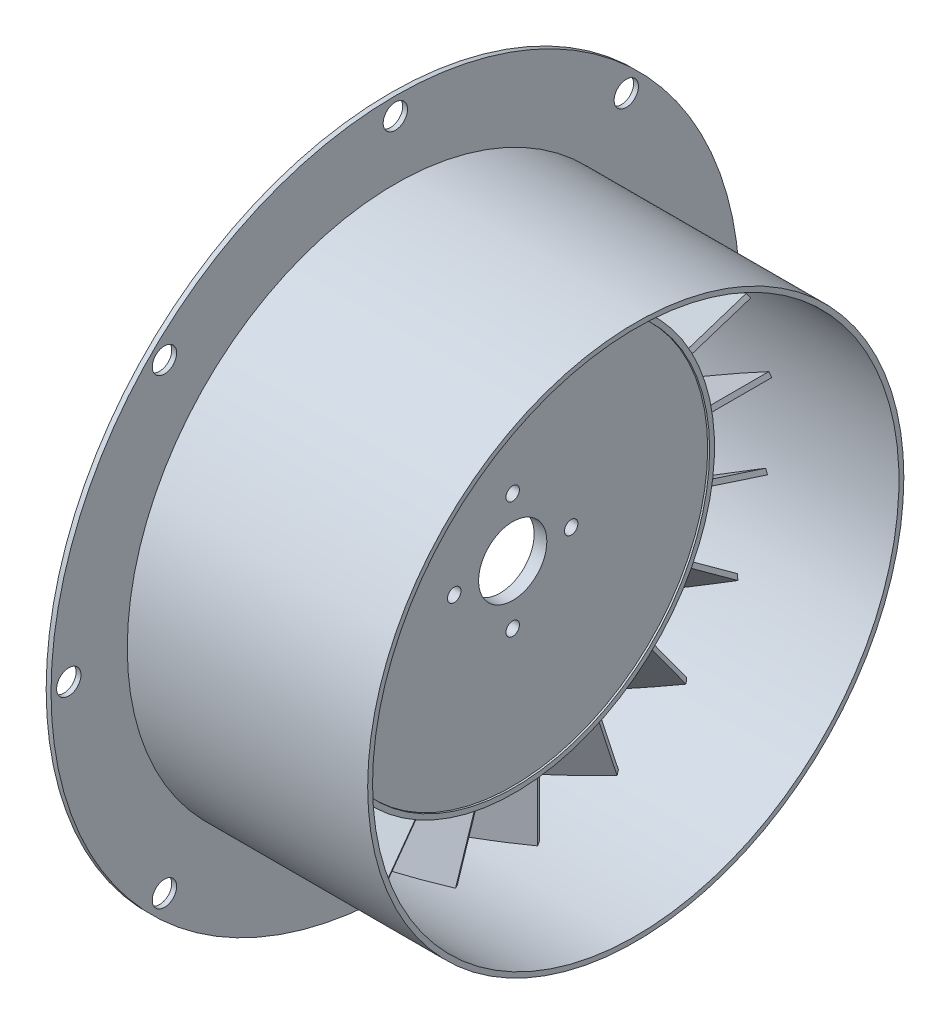
SolidWorks part; units mm, degrees
ref_plane "Front Plane" through (0, 0, 0) normal (0, 0, 1) x (1, 0, 0)
ref_plane "Top Plane" through (0, 0, 0) normal (0, 1, 0) x (1, 0, 0)
ref_plane "Right Plane" through (0, 0, 0) normal (1, 0, 0) x (0, 0, -1)
sketch "Sketch1" plane through (0, 0, 0) normal (0, 1, 0) x (1, 0, 0)
  line L0 (3.302, 0) -> (3.302, 50.8)
  line L1 (3.302, 50.8) -> (3.81, 50.8)
  line L2 (3.81, 50.8) -> (3.81, 52.07)
  line L3 (3.81, 52.07) -> (-25.4, 52.07)
  line L4 (-25.4, 52.07) -> (-25.4, 50.8)
  line L5 (-25.4, 50.8) -> (0, 50.8)
  line L6 (0, 50.8) -> (0, 0)
  line L7 (0, 0) -> (3.302, 0)
  dimension "D1" = 3.302
  dimension "D2" = 1.27
  dimension "D3" = 50.8
  dimension "D4" = 29.21
  dimension "D5" = 25.4
revolve "Revolve1" add sketch "Sketch1" angle 360 about L7
ref_plane "Plane1" through (0, 0, 83.82) normal (0, 0, 1) x (1, 0, 0)
sketch "Sketch2" plane through (0, 0, 83.82) normal (0, 0, 1) x (1, 0, 0)
  line L0 (-24.3107, 7.0701) -> (2.0857, -8.1699)
  line L1 (2.0857, -8.1699) -> (2.7207, -7.0701)
  line L3 (2.7207, -7.0701) -> (-23.6757, 8.1699)
  line L4 (-23.6757, 8.1699) -> (-24.3107, 7.0701)
  line L5 (-25.4, 0) -> (3.81, 0) construction
  line L6 (-25.4, 52.07) -> (-25.4, -52.07) construction
  line L7 (3.81, -52.07) -> (3.81, 52.07) construction
  line L8 (-11.1125, -0.5499) -> (-10.4775, 0.5499) construction
  point P4 (-10.795, 0)
  point P13 (-10.795, 0)
  dimension "D1" = 1.27
  dimension "D2" = 30
  dimension "D3" = 30.48
extrude "Boss-Extrude1" add sketch "Sketch2" along normal blind 16.51 from surface starting at face at (-25.4, 0, 52.07)
pattern_circular "CirPattern15" count 20 over 360 about axis through (3.81, 0, 0) along (-1, 0, 0) of "Boss-Extrude1"
sketch "Sketch7" plane through (3.302, 0, 0) normal (1, 0, 0) x (0, 0, -1)
  circle A0 centre (0, 15.24) radius 1.7526
  circle A1 centre (0, 0) radius 8.89
  circle A2 centre (15.24, 0) radius 1.7526
  circle A3 centre (0, -15.24) radius 1.7526
  circle A4 centre (-15.24, 0) radius 1.7526
  point P14 (0, 0)
  dimension "D1" = 3.5052
  dimension "D3" = 17.78
  dimension "D2" = 15.24
  dimension "D4" = 4
extrude "Cut-Extrude1" cut sketch "Sketch7" against normal through all
sketch "Sketch8" plane through (0, 0, 0) normal (0, 0, 1) x (1, 0, 0)
  line L0 (35.3606, 69.85) -> (35.3606, 68.58)
  line L1 (35.3606, 68.58) -> (-28.5393, 68.58)
  line L2 (-28.5393, -76.2) -> (-28.5393, 76.2) construction
  line L3 (-28.5393, 68.58) -> (-28.5393, 89.7168)
  line L5 (-28.5393, 89.7168) -> (-27.2693, 89.7168)
  line L6 (-27.2693, 89.7168) -> (-27.2693, 69.85)
  line L7 (-27.2693, 69.85) -> (35.3606, 69.85)
  line L8 (35.3606, -69.85) -> (35.3606, 69.85) construction
  line L9 (-93.6879, 0) -> (-7.1026, 0) construction
  line L10 (0, 0) -> (79.505, 0) construction
  dimension "D1" = 68.58
  dimension "D2" = 1.27
  dimension "D3" = 1.27
revolve "Revolve2" add sketch "Sketch8" angle 360 about L10
sketch "Sketch9" plane through (-27.2693, 0, 0) normal (1, 0, 0) x (0, 0, -1)
  circle A0 centre (0, 85.09) radius 3.175
  circle A1 centre (60.1677, 60.1677) radius 3.175
  circle A2 centre (85.09, 0) radius 3.175
  circle A3 centre (60.1677, -60.1677) radius 3.175
  circle A4 centre (0, -85.09) radius 3.175
  circle A5 centre (-60.1677, -60.1677) radius 3.175
  circle A6 centre (-85.09, 0) radius 3.175
  circle A7 centre (-60.1677, 60.1677) radius 3.175
  point P19 (0, 0)
  dimension "D1" = 6.35
  dimension "D2" = 85.09
  dimension "D3" = 8
extrude "Cut-Extrude2" cut sketch "Sketch9" against normal blind 2.54
